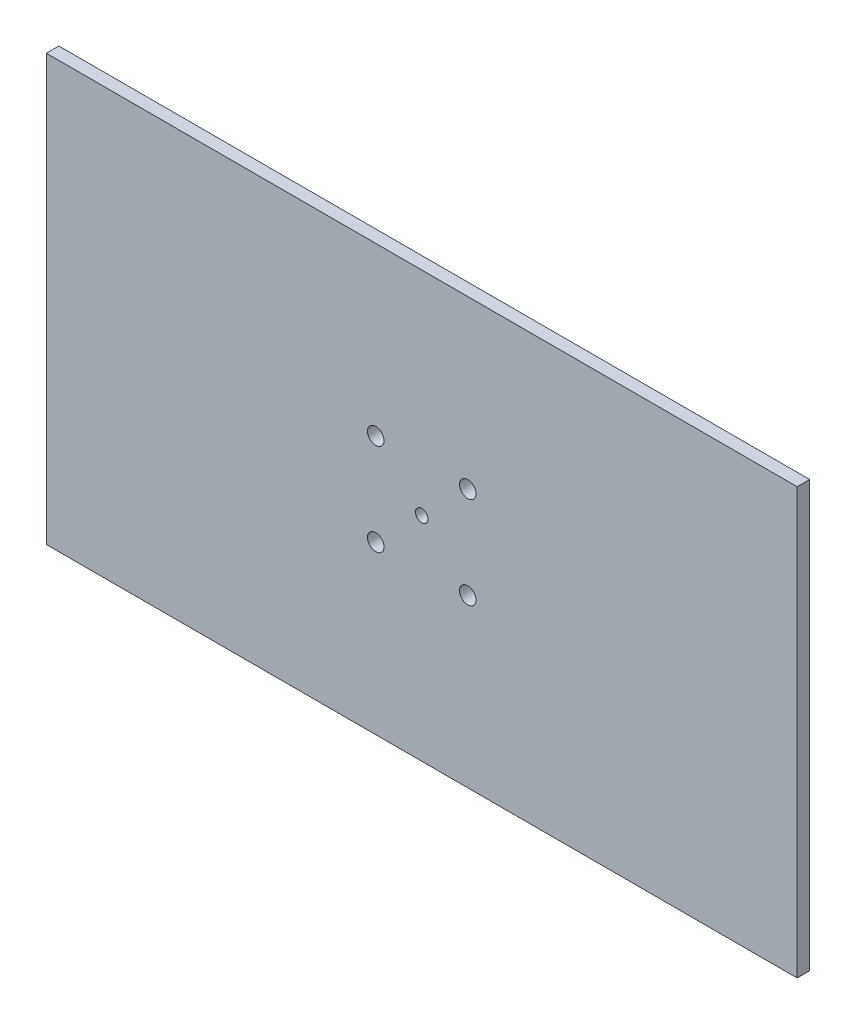
SolidWorks part; units mm, degrees
ref_plane "前视基准面" through (0, 0, 0) normal (0, 0, 1) x (1, 0, 0)
ref_plane "上视基准面" through (0, 0, 0) normal (0, 1, 0) x (1, 0, 0)
ref_plane "右视基准面" through (0, 0, 0) normal (1, 0, 0) x (0, 0, -1)
sketch "草图1" plane through (0, 0, 0) normal (0, 0, 1) x (1, 0, 0)
  line L0 (-18.3848, 18.3848) -> (0, 0) construction
  line L1 (150, -125) -> (-150, -125)
  line L2 (150, -125) -> (150, 125)
  line L3 (150, 125) -> (-150, 125)
  line L4 (-150, -125) -> (-150, 125)
  line L5 (150, -125) -> (-150, 125) construction
  line L6 (150, 125) -> (-150, -125) construction
  line L7 (0, 0) -> (0, 75.2853) construction
  line L8 (0, 0) -> (89.5261, 0) construction
  circle A0 centre (-18.3848, 18.3848) radius 3.3
  circle A1 centre (18.3848, 18.3848) radius 3.3
  circle A2 centre (18.3848, -18.3848) radius 3.3
  circle A3 centre (-18.3848, -18.3848) radius 3.3
  circle A4 centre (0, 0) radius 2.5
  point P0 (0, 0)
  dimension "D3" = 6.6
  dimension "D6" = 5
  dimension "D1" = 250
  dimension "D2" = 300
  dimension "D4" = 26
  dimension "D5" = 45
extrude "凸台-拉伸1" add sketch "草图1" along normal blind 5
sketch "草图2" plane through (0, 0, 5) normal (0, 0, 1) x (1, 0, 0)
  line L0 (150, -125) -> (150, 125) construction
  line L1 (-150, 125) -> (150, 125)
  line L2 (-150, 125) -> (-150, 85)
  line L3 (-150, 85) -> (150, 85)
  line L4 (150, 125) -> (150, 85)
  line L6 (-150, -125) -> (150, -125)
  line L7 (-150, -125) -> (-150, -85)
  line L8 (-150, -85) -> (150, -85)
  line L9 (150, -125) -> (150, -85)
  dimension "D1" = 40
extrude "切除-拉伸1" cut sketch "草图2" against normal through all
